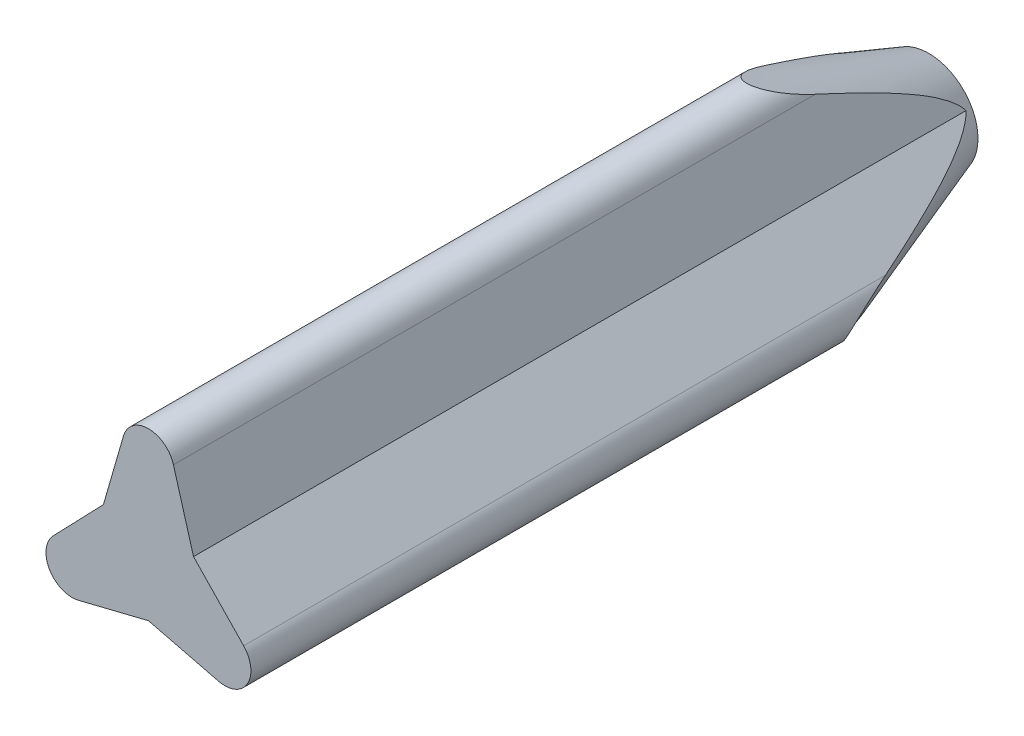
SolidWorks part; units mm, degrees
material "ABS"
ref_plane "Front Plane" through (0, 0, 0) normal (0, 0, 1) x (1, 0, 0)
ref_plane "Top Plane" through (0, 0, 0) normal (0, 1, 0) x (1, 0, 0)
ref_plane "Right Plane" through (0, 0, 0) normal (1, 0, 0) x (0, 0, -1)
sketch "Sketch1" plane through (0, 0, 0) normal (0, 0, 1) x (1, 0, 0)
  line L0 (0, 0) -> (0, 14) construction
  line L1 (0, 0) -> (-12.1244, -7) construction
  line L2 (0, 0) -> (12.1244, -7)
  line L3 (-12.1244, -7) -> (-3.4641, 2)
  line L4 (-3.4641, 2) -> (0, 14)
  line L5 (0, 14) -> (3.4641, 2)
  line L6 (0, -4) -> (12.1244, -7)
  line L7 (-12.1244, -7) -> (0, -4)
  line L8 (3.4641, 2) -> (12.1244, -7)
  circle A0 centre (0, 0) radius 14 construction
  circle A1 centre (0, 0) radius 10 construction
  circle A2 centre (0, 0) radius 4 construction
  dimension "D1" = 28
  dimension "D2" = 20
  dimension "D5" = 8
  dimension "D3" = 120
  dimension "D4" = 120
extrude "Boss-Extrude1" add sketch "Sketch1" along normal blind 60 contours L8 L5 L4 L3 L7 L6 region at (-7.5631, -2.7224, 0)
fillet "Fillet1" radius 2 3 edges at (12.1244, -7, 30) (-12.1244, -7, 30) (0, 14, 30)
sketch "Sketch2" plane through (0, 0, 0) normal (1, 0, 0) x (0, 0, -1)
  line L0 (0, 2) -> (0, 3.7889) construction
  line L1 (0, 2) -> (0, 7.3436) construction
  line L2 (-60, 2) -> (0, 2) construction
  line L3 (0, 3.7889) -> (-14, 8.7889)
  line L4 (0, 8.7889) -> (-60, 8.7889) construction
  line L5 (-14, 8.7889) -> (0, 8.7889)
  line L6 (0, 8.7889) -> (0, 3.7889)
  line L7 (0, 3.7889) -> (0, 8.7889)
  line L8 (-14, 8.7889) -> (0, 8.7889)
  dimension "D1" = 14
  dimension "D2" = 5
sketch "Sketch4" plane through (0, 0, 0) normal (1, 0, 0) x (0, 0, -1)
  line L0 (0, 0) -> (7.8198, 0) construction
revolve "Cut-Revolve1" cut sketch "Sketch2" angle 360 about L0 region at (0, 7.1222, 4.6667)
